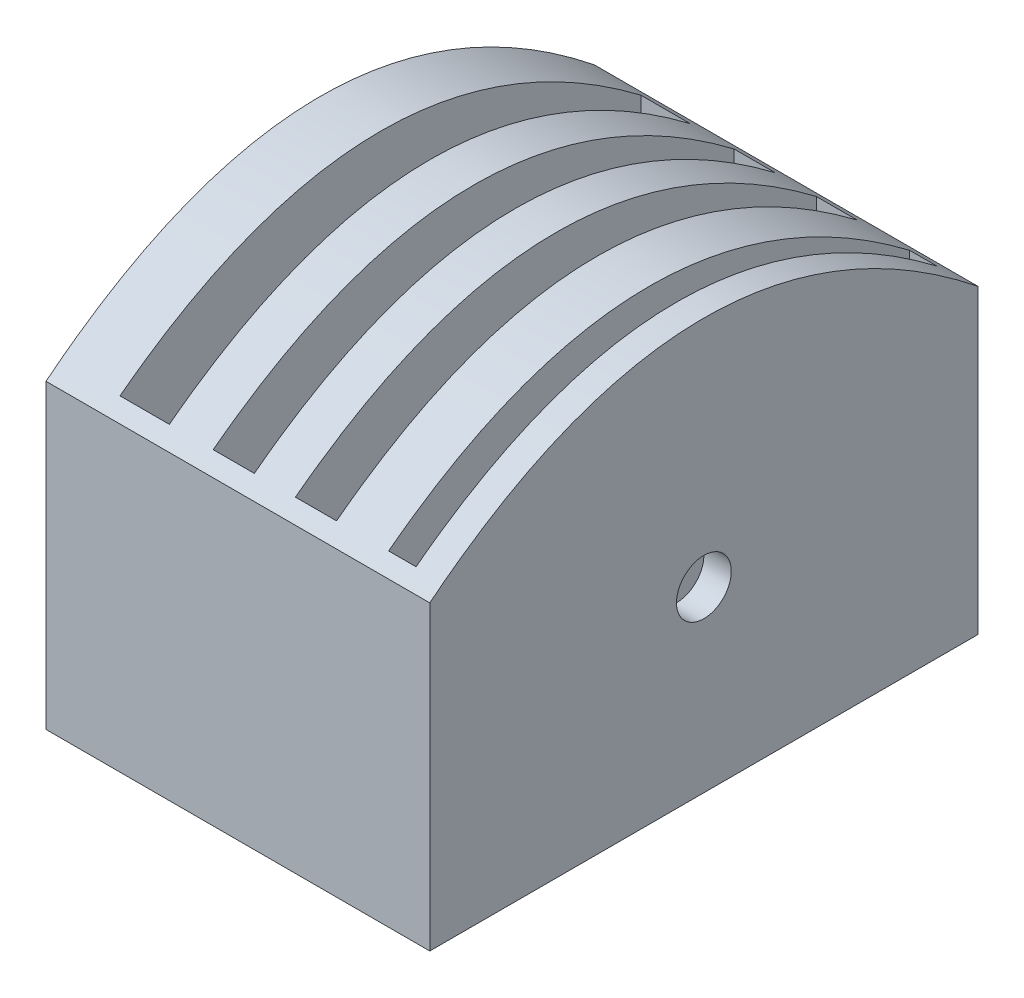
SolidWorks part; units mm, degrees
ref_plane "Front Plane" through (0, 0, 0) normal (0, 0, 1) x (1, 0, 0)
ref_plane "Top Plane" through (0, 0, 0) normal (0, 1, 0) x (1, 0, 0)
ref_plane "Right Plane" through (0, 0, 0) normal (1, 0, 0) x (0, 0, -1)
sketch "Sketch1" plane through (0, 0, 0) normal (1, 0, 0) x (0, 0, -1)
  line L2 (-100, 85) -> (-100, -25)
  line L3 (-100, -25) -> (100, -25)
  line L4 (100, 85) -> (100, -25)
  spline S0 degree 2 poles (-100, 85) (0, 165) (100, 85) knots 0 0 0 1 1 1
  point P4 (-100, 85)
  point P5 (100, 85)
  dimension "D1" = 200
  dimension "D2" = 100
  dimension "D3" = 110
  dimension "D4" = 110
  dimension "D5" = 40
  dimension "D6" = 100
  dimension "D7" = 125
extrude "Base" add sketch "Sketch1" along normal blind 140
ref_plane "New Top" through (0, 125, 0) normal (0, 1, 0) x (1, 0, 0)
sketch "Sketch3" plane through (0, 125, 0) normal (0, 1, 0) x (1, 0, 0)
  line L1 (101, 95) -> (86, 95)
  line L2 (101, 95) -> (101, -95)
  line L3 (101, -95) -> (86, -95)
  line L4 (86, 95) -> (86, -95)
  line L7 (140, 100) -> (0, 100) construction
  line L8 (71, 95) -> (56, 95)
  line L9 (71, 95) -> (71, -95)
  line L10 (71, -95) -> (56, -95)
  line L11 (56, 95) -> (56, -95)
  line L12 (140, -100) -> (0, -100) construction
  line L13 (0, 100) -> (0, -100) construction
  dimension "D1" = 56
  dimension "D2" = 15
  dimension "D3" = 15
  dimension "D4" = 15
  dimension "D5" = 5
  dimension "D6" = 5
  dimension "D7" = 5
  dimension "D8" = 5
sketch "Sketch4" plane through (0, 125, 0) normal (0, 1, 0) x (1, 0, 0)
  line L1 (40, 95) -> (22, 95)
  line L2 (40, 95) -> (40, -95)
  line L3 (40, -95) -> (22, -95)
  line L4 (22, 95) -> (22, -95)
  line L5 (140, 100) -> (0, 100) construction
  line L6 (140, -100) -> (0, -100) construction
  line L7 (0, 100) -> (0, -100) construction
  dimension "D1" = 22
  dimension "D2" = 18
  dimension "D3" = 5
  dimension "D4" = 5
sketch "Sketch5" plane through (0, 125, 0) normal (0, 1, 0) x (1, 0, 0)
  line L0 (140, -100) -> (140, 100) construction
  line L1 (130, 95) -> (120, 95)
  line L2 (130, 95) -> (130, -95)
  line L3 (130, -95) -> (120, -95)
  line L4 (120, 95) -> (120, -95)
  line L5 (140, 100) -> (0, 100) construction
  line L6 (140, -100) -> (0, -100) construction
  dimension "D1" = 10
  dimension "D2" = 10
  dimension "D3" = 5
  dimension "D4" = 5
extrude "Flaps Cut" cut sketch "Sketch5" against normal up to surface (150 mm away) up to face at (70, -25, 0)
extrude "Throttle Cut" cut sketch "Sketch3" against normal up to surface (150 mm away) up to face at (125, -25, 0)
extrude "Wing Sweep Cut" cut sketch "Sketch4" against normal up to surface (150 mm away) up to face at (93.5, -25, 0)
sketch "Sketch6" plane through (0, 0, 0) normal (-1, 0, 0) x (0, 0, 1)
  circle A0 centre (0, 40) radius 10
  dimension "D1" = 20
  dimension "D2" = 40
extrude "Cut-Extrude1" cut sketch "Sketch6" against normal up to next from surface starting at face at (130, 31.95, -23.75)
